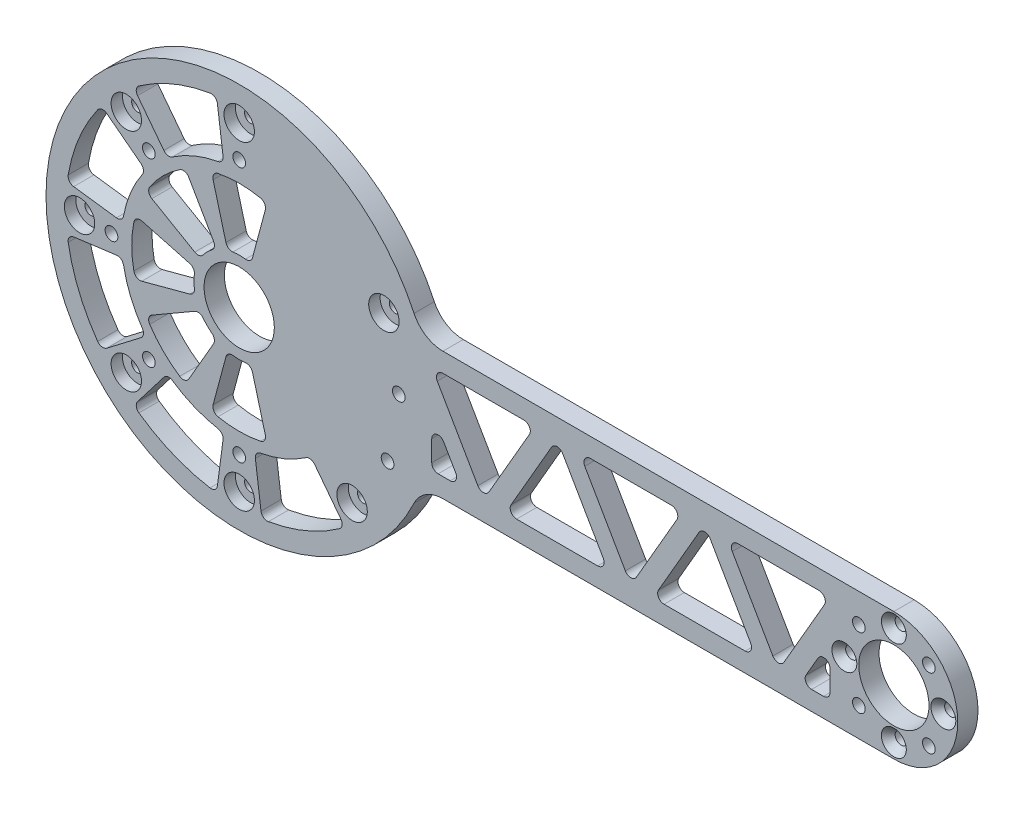
SolidWorks part; units mm, degrees
material "Balsa"
ref_plane "Front Plane" through (0, 0, 0) normal (0, 0, 1) x (1, 0, 0)
ref_plane "Top Plane" through (0, 0, 0) normal (0, 1, 0) x (1, 0, 0)
ref_plane "Right Plane" through (0, 0, 0) normal (1, 0, 0) x (0, 0, -1)
sketch "Sketch1" plane through (0, 0, 0) normal (0, 0, 1) x (1, 0, 0)
  line L0 (57.0986, -20) -> (205, -20)
  line L1 (57.0986, 20) -> (205, 20)
  line L2 (45.3154, 21.1309) -> (0, 0) construction
  line L3 (0, 0) -> (35.3553, -35.3553) construction
  line L4 (49.9788, 1.4542) -> (0, 0) construction
  line L5 (0, 0) -> (46.4674, -18.4603) construction
  arc A0 (57.0986, -20) -> (57.0986, 20) centre (0, 0) cw
  arc A1 (205, 20) -> (205, -20) centre (205, 0) cw
  circle A2 centre (0, 0) radius 60.5 construction
  circle A3 centre (0, 0) radius 11
  circle A4 centre (45.3154, 21.1309) radius 1.8986
  circle A5 centre (0, 0) radius 40 construction
  circle A6 centre (0, 0) radius 50 construction
  circle A7 centre (49.9788, 1.4542) radius 1.9939
  circle A8 centre (205, 0) radius 11
  circle A9 centre (46.4674, -18.4603) radius 1.9939
  circle A10 centre (205, 0) radius 15.5 construction
  circle A11 centre (205, -15.5) radius 1.8987
  circle A12 centre (215.9602, -10.9602) radius 1.9939
  circle A13 centre (189.5, 0) radius 1.8987
  circle A14 centre (194.0398, -10.9602) radius 1.9939
  circle A15 centre (205, 15.5) radius 1.8987
  circle A16 centre (194.0398, 10.9602) radius 1.9939
  circle A17 centre (220.5, 0) radius 1.8987
  circle A18 centre (215.9602, 10.9602) radius 1.9939
  circle A29 centre (0, -40) radius 1.9939
  circle A30 centre (0, -50) radius 1.8986
  circle A37 centre (-28.2843, -28.2843) radius 1.9939
  circle A38 centre (-35.3553, -35.3553) radius 1.8986
  circle A39 centre (-40, 0) radius 1.9939
  circle A40 centre (-50, 0) radius 1.8986
  circle A41 centre (-28.2843, 28.2843) radius 1.9939
  circle A42 centre (-35.3553, 35.3553) radius 1.8986
  circle A43 centre (0, 40) radius 1.9939
  circle A44 centre (0, 50) radius 1.8986
  circle A45 centre (28.2843, 28.2843) radius 1.9939 construction
  circle A46 centre (35.3553, 35.3553) radius 1.8986 construction
  circle A47 centre (40, 0) radius 1.9939 construction
  circle A48 centre (50, 0) radius 1.8986 construction
  circle A49 centre (28.2843, -28.2843) radius 1.9939 construction
  circle A50 centre (35.3553, -35.3553) radius 1.8986
  dimension "D1" = 121
  dimension "D4" = 22
  dimension "D6" = 100
  dimension "D7" = 80
  dimension "D8" = 70
  dimension "D9" = 3.7973
  dimension "D10" = 3.9878
  dimension "D15" = 3.7973
  dimension "D16" = 3.9878
  dimension "D17" = 3.7973
  dimension "D18" = 3.9878
  dimension "D5" = 31
  dimension "D19" = 3.9878
  dimension "D2" = 40
  dimension "D3" = 205
  dimension "D11" = 45
  dimension "D13" = 23.333
  dimension "D14" = 23.333
  dimension "D12" = 4
  dimension "D21" = 8
extrude "Boss-Extrude1" add sketch "Sketch1" along normal blind 6.35
fillet "Fillet1" radius 10 2 edges at (57.0986, -20, 3.175) (57.0986, 20, 3.175)
sketch "Sketch2" plane through (0, 0, 6.35) normal (0, 0, 1) x (1, 0, 0)
  line L0 (60.2923, 14) -> (92.624, 14)
  line L1 (92.624, 14) -> (76.4581, -14)
  line L2 (76.4581, -14) -> (60.2923, 14)
  line L3 (83.3864, -14) -> (99.5522, 14)
  line L4 (99.5522, 14) -> (115.718, -14)
  line L5 (115.718, -14) -> (83.3864, -14)
  line L6 (106.4804, 14) -> (122.6462, -14)
  line L7 (122.6462, -14) -> (138.812, 14)
  line L8 (138.812, 14) -> (106.4804, 14)
  line L9 (129.5744, -14) -> (145.7402, 14)
  line L10 (145.7402, 14) -> (161.906, -14)
  line L11 (161.906, -14) -> (129.5744, -14)
  line L12 (152.6684, 14) -> (168.8342, -14)
  line L13 (168.8342, -14) -> (185, 14)
  line L14 (185, 14) -> (152.6684, 14)
  line L15 (60.2923, 2) -> (60.2923, -14)
  line L16 (60.2923, -14) -> (69.5299, -14)
  line L17 (69.5299, -14) -> (60.2923, 2)
  line L18 (185, 2) -> (185, -14)
  line L19 (185, -14) -> (175.7624, -14)
  line L20 (175.7624, -14) -> (185, 2)
  line L21 (205, 20) -> (63.7985, 20) construction
  line L22 (63.7985, -20) -> (205, -20) construction
  arc A0 (205, -20) -> (205, 20) centre (205, 0) ccw construction
  point P25 (225, 0)
  dimension "D1" = 60
  dimension "D2" = 60
  dimension "D3" = 6
  dimension "D4" = 6
  dimension "D5" = 6
  dimension "D6" = 6
  dimension "D7" = 6
  dimension "D8" = 6
  dimension "D9" = 6
  dimension "D10" = 6
  dimension "D11" = 40
extrude "Cut-Extrude1" cut sketch "Sketch2" against normal through all
fillet "Fillet2" radius 2 21 edges at (175.7624, -14, 3.175) (69.5299, -14, 3.175) (129.5744, -14, 3.175) (83.3864, -14, 3.175) (122.6462, -14, 3.175) (76.4581, -14, 3.175) (60.2923, -14, 3.175) (60.2923, 2, 3.175) (99.5522, 14, 3.175) (145.7402, 14, 3.175) (185, 2, 3.175) (115.718, -14, 3.175) (161.906, -14, 3.175) (185, -14, 3.175) (168.8342, -14, 3.175) (185, 14, 3.175) (138.812, 14, 3.175) (92.624, 14, 3.175) (152.6684, 14, 3.175) (106.4804, 14, 3.175) (60.2923, 14, 3.175)
other "Move Face1" [suppressed] offset 0.08 parameters "D1"=0.08
sketch "Sketch3" plane through (0, 0, 6.35) normal (0, 0, 1) x (1, 0, 0)
  line L0 (0, 0) -> (-71.2971, 0) construction
  line L1 (-32.5034, 8.7093) -> (-13.692, 3.6688)
  line L2 (-13.692, -3.6688) -> (-32.5034, -8.7093)
  arc A0 (-13.692, -3.6688) -> (-13.692, 3.6688) centre (0, 0) cw
  arc A1 (-32.5034, -8.7093) -> (-32.5034, 8.7093) centre (0, 0) cw
  circle A2 centre (0, 0) radius 11 construction
  circle A3 centre (-40, 0) radius 1.9939 construction
  point P7 (-14.175, 0)
  point P10 (-33.65, 0)
  dimension "D2" = 3.175
  dimension "D3" = 6.35
  dimension "D1" = 30
extrude "Cut-Extrude2" cut sketch "Sketch3" against normal through all
fillet "Fillet3" radius 2 4 edges at (-32.5034, -8.7093, 3.175) (-13.692, -3.6688, 3.175) (-13.692, 3.6688, 3.175) (-32.5034, 8.7093, 3.175)
pattern_circular "CirPattern1" count 8 over 360 about axis through (0, 0, 6.35) along (0, 0, -1) skipping 3, 4, 5 of "Fillet3", "Cut-Extrude2"
sketch "Sketch5" plane through (0, 0, 6.35) normal (0, 0, 1) x (1, 0, 0)
  line L0 (-78.0787, 0) -> (0, 0) construction
  line L1 (0, 0) -> (-81.1598, 33.6175) construction
  line L2 (-53.8602, 7.0908) -> (-36.51, 4.8066)
  line L3 (-43.0989, 33.071) -> (-29.2152, 22.4176)
  arc A0 (-36.51, 4.8066) -> (-29.2152, 22.4176) centre (0, 0) cw
  arc A1 (-53.8602, 7.0908) -> (-43.0989, 33.071) centre (0, 0) cw
  circle A2 centre (-35.3553, 35.3553) radius 1.8987 construction
  circle A3 centre (-28.2843, 28.2843) radius 1.9939 construction
  circle A4 centre (-35.3553, 35.3553) radius 1.8986 construction
  circle A5 centre (-28.2843, 28.2843) radius 1.9939 construction
  arc A6 (54.7491, 25.7447) -> (54.7491, -25.7447) centre (0, 0) ccw construction
  arc A7 (-32.9888, 6.6379) -> (-32.9888, -6.6379) centre (0, 0) ccw construction
  point P8 (-34.0219, 14.0923)
  dimension "D3" = 6.175
  dimension "D4" = 3.175
  dimension "D1" = 22.5
  dimension "D2" = 30
extrude "Cut-Extrude4" cut sketch "Sketch5" against normal through all
fillet "Fillet5" radius 2 4 edges at (-53.8602, 7.0908, 3.175) (-36.51, 4.8066, 3.175) (-29.2152, 22.4176, 3.175) (-43.0989, 33.071, 3.175)
pattern_circular "CirPattern3" count 8 over 360 about axis through (0, 0, 6.35) along (0, 0, -1) skipping 2, 3, 4 of "Fillet5", "Cut-Extrude4"
chamfer "Chamfer1" distance 2.301 angle 41 4 edges at (222.3986, 0, 6.35) (206.8987, -15.5, 6.35) (191.3987, 0, 6.35) (206.8987, 15.5, 6.35) first distance on face at (222.3986, 0, 6.35) first distance on face at (206.8987, -15.5, 6.35) first distance on face at (191.3987, 0, 6.35) first distance on face at (206.8987, 15.5, 6.35)
sketch "Sketch6" plane through (0, 0, 6.35) normal (0, 0, 1) x (1, 0, 0)
  circle A0 centre (45.3154, 21.1309) radius 1.8987 construction
  circle A1 centre (35.3553, -35.3553) radius 1.8987 construction
  circle A2 centre (0, -50) radius 1.8986 construction
  circle A3 centre (-35.3553, -35.3553) radius 1.8987 construction
  circle A4 centre (-50, 0) radius 1.8987 construction
  circle A5 centre (-35.3553, 35.3553) radius 1.8987 construction
  circle A6 centre (0, 50) radius 1.8986 construction
  circle A7 centre (45.3154, 21.1309) radius 1.8986
  circle A8 centre (35.3553, -35.3553) radius 1.8986
  circle A9 centre (0, -50) radius 1.8986
  circle A10 centre (-35.3553, -35.3553) radius 1.8986
  circle A11 centre (-50, 0) radius 1.8986
  circle A12 centre (-35.3553, 35.3553) radius 1.8986
  circle A13 centre (0, 50) radius 1.8986
  circle A14 centre (0, 50) radius 4.7625
  circle A15 centre (-35.3553, 35.3553) radius 4.7625
  circle A16 centre (-50, 0) radius 4.7625
  circle A17 centre (-35.3553, -35.3553) radius 4.7625
  circle A18 centre (0, -50) radius 4.7625
  circle A19 centre (35.3553, -35.3553) radius 4.7625
  circle A20 centre (45.3154, 21.1309) radius 4.7625
  dimension "D1" = 9.525
extrude "Cut-Extrude5" cut sketch "Sketch6" against normal blind 3.5719
